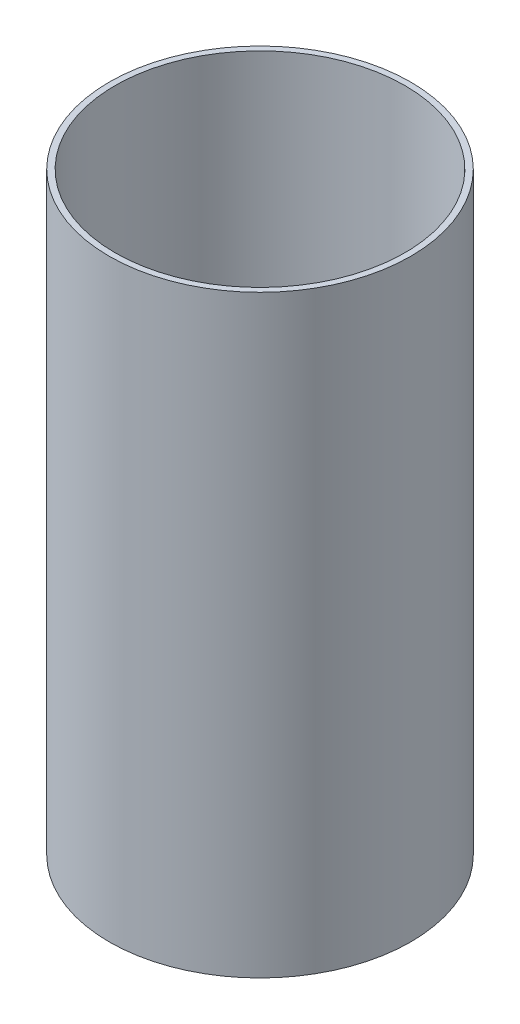
SolidWorks part; units mm, degrees
ref_plane "Front Plane" through (0, 0, 0) normal (0, 0, 1) x (1, 0, 0)
ref_plane "Top Plane" through (0, 0, 0) normal (0, 1, 0) x (1, 0, 0)
ref_plane "Right Plane" through (0, 0, 0) normal (1, 0, 0) x (0, 0, -1)
sketch "Sketch1" plane through (0, 0, 0) normal (0, 1, 0) x (1, 0, 0)
  circle A0 centre (0, 0) radius 24.4
  circle A1 centre (0, 0) radius 25.4
  dimension "D1" = 1
  dimension "D2" = 50.8
extrude "Boss-Extrude1" add sketch "Sketch1" along normal blind 100
